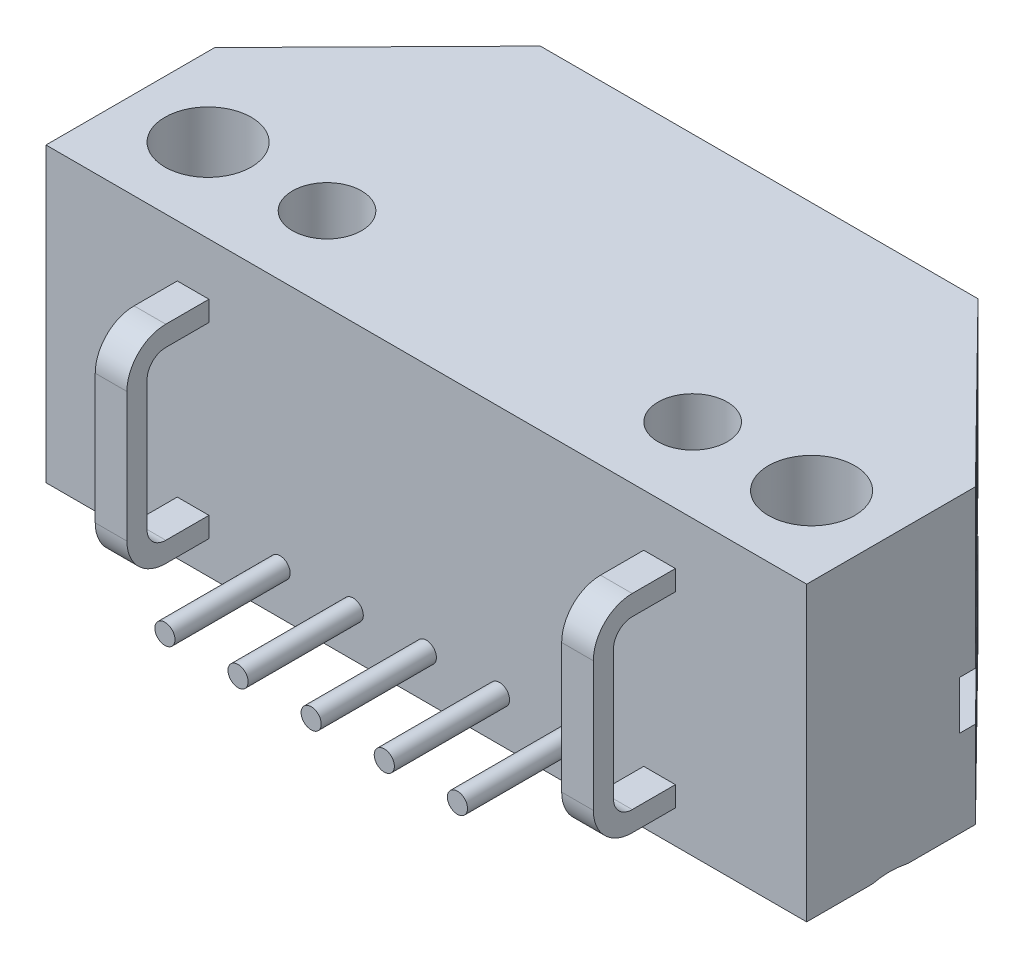
SolidWorks part; units mm, degrees
ref_plane "Ebene vorne" through (0, 0, 0) normal (0, 0, 1) x (1, 0, 0)
ref_plane "Ebene oben" through (0, 0, 0) normal (0, 1, 0) x (1, 0, 0)
ref_plane "Ebene rechts" through (0, 0, 0) normal (1, 0, 0) x (0, 0, -1)
sketch "Skizze1" plane through (0, 0, 0) normal (0, 1, 0) x (1, 0, 0)
  line L0 (0, 18.4765) -> (0, -25.5527) construction
  line L1 (-10.8738, -15.75) -> (10.2359, -15.75) construction
  line L2 (-12.2657, 0) -> (14.2955, 0) construction
  line L3 (-13.21, -18.65) -> (-13.21, -12.79)
  line L4 (-13.21, -12.79) -> (-7.6, -7.09)
  line L5 (-7.6, -7.09) -> (7.6, -7.09)
  line L6 (-13.21, -18.65) -> (13.21, -18.65)
  line L7 (13.21, -18.65) -> (13.21, -12.79)
  line L8 (13.21, -12.79) -> (7.6, -7.09)
  circle A0 centre (-10.48, -15.75) radius 1.385
  circle A1 centre (10.48, -15.75) radius 1.385
  point P17 (0, -18.65)
  point P19 (0, -7.09)
  dimension "D2" = 2.77
  dimension "D1" = 15.75
  dimension "D3" = 26.42
  dimension "D4" = 11.56
  dimension "D5" = 5.7
  dimension "D6" = 15.2
  dimension "D7" = 2.9
  dimension "D8" = 20.96
extrude "Aufsatz-Linear austragen1" add sketch "Skizze1" along normal blind 6.74 and the other way blind 3.42
sketch "Skizze2" plane through (0, 0, 0) normal (1, 0, 0) x (0, 0, -1)
  line L0 (-22.1031, 0) -> (8.1421, 0) construction
  line L1 (-13.35, 1.28) -> (2.6852, 1.28)
  line L2 (-13.35, 1.28) -> (-13.35, -0.4)
  line L3 (-13.35, -0.4) -> (2.6852, -0.4)
  line L4 (2.6852, 1.28) -> (2.6852, -0.4)
  line L5 (-7.09, -3.42) -> (-12.79, -3.42) construction
  line L6 (-7.09, 6.74) -> (-12.79, 6.74) construction
  line L7 (-18.65, -3.42) -> (-18.65, 6.74) construction
  dimension "D1" = 3.02
  dimension "D2" = 5.46
  dimension "D3" = 1.68
  dimension "D4" = 5.3
extrude "Schnitt-Linear austragen1" cut sketch "Skizze2" against normal through all and the other way through all
sketch "Skizze3" plane through (0, 6.74, 0) normal (0, 1, 0) x (1, 0, 0)
  line L0 (0, -26.155) -> (0, 11.9895) construction
  line L1 (21.4405, 0) -> (-13.3752, 0) construction
  line L2 (-13.21, -18.65) -> (13.21, -18.65) construction
  circle A0 centre (6.35, -15.75) radius 1.2
  circle A1 centre (-6.35, -15.75) radius 1.2
  dimension "D3" = 2.4
  dimension "D1" = 12.7
  dimension "D2" = 2.9
extrude "Schnitt-Linear austragen2" cut sketch "Skizze3" against normal blind 2.16
sketch "Skizze4" plane through (0, 0, 18.65) normal (0, 0, 1) x (1, 0, 0)
  line L0 (0, -9.3032) -> (0, 8.8775) construction
  line L1 (0, -1.9) -> (8.502, -1.9) construction
  line L2 (-13.21, -3.42) -> (13.21, -3.42) construction
  circle A0 centre (0, -1.9) radius 0.35
  circle A1 centre (2.54, -1.9) radius 0.35
  circle A2 centre (5.08, -1.9) radius 0.35
  circle A3 centre (-2.54, -1.9) radius 0.35
  circle A4 centre (-5.08, -1.9) radius 0.35
  dimension "D1" = 0.7
  dimension "D2" = 2.54
  dimension "D3" = 2.54
  dimension "D4" = 1.52
extrude "Aufsatz-Linear austragen2" add sketch "Skizze4" along normal blind 4
ref_plane "Ebene1" through (8.1, 0, 0) normal (1, 0, 0) x (0, 0, -1)
sketch "Skizze5" plane through (8.1, 0, 0) normal (1, 0, 0) x (0, 0, -1)
  line L0 (-18.65, -1.92) -> (-20.15, -1.92)
  line L1 (-21.15, -0.92) -> (-21.15, 3.58)
  line L2 (-20.15, 4.58) -> (-18.65, 4.58)
  line L3 (-18.65, -3.42) -> (-18.65, 6.74) construction
  line L4 (-18.65, -3.42) -> (-12.79, -3.42) construction
  arc A0 (-20.15, 4.58) -> (-21.15, 3.58) centre (-20.15, 3.58) ccw
  arc A1 (-21.15, -0.92) -> (-20.15, -1.92) centre (-20.15, -0.92) ccw
  point P10 (-21.15, 4.58)
  point P13 (-21.15, -1.92)
  dimension "D4" = 1
  dimension "D1" = 1.5
  dimension "D2" = 6.5
  dimension "D3" = 2.5
extrude "Linear-Austragen-Dünn1" add sketch "Skizze5" along normal blind 0.55 and the other way blind 0.55 thin thin type mid plane wall 0.7
mirror "Spiegeln1" about plane through (0, 0, 0) normal (1, 0, 0) of "Linear-Austragen-Dünn1"
ref_axis "Achse1" through (0, -3.928, 0) along (0, 1, 0)
hole_wizard "Formsenkung für M3 Senkschraube mit Schlitz/Kreuzschlitz1" positions "Skizze7" profile "Skizze6" countersink size "M3" standard "ANSI Metrisch"
sketch "Skizze7" plane through (0, -3.42, 0) normal (0, -1, 0) x (-1, 0, 0)
  point P0 (-10.48, -15.75)
  point P3 (10.48, -15.75)
sketch "Skizze6" plane through (10.48, -3.42, 15.75) normal (1, 0, 0) x (0, 0, -1)
  line L0 (0, 0) -> (0, 11.9013)
  line L1 (0, 11.9013) -> (1.5, 11)
  line L2 (1.5, 11) -> (1.5, 1.3)
  line L3 (1.5, 1.3) -> (2.8, 0)
  line L5 (2.8, 0) -> (0, 0)
  line L6 (-1.5, 1.3) -> (-2.8, 0) construction
  line L10 (0, 11.9013) -> (-1.5, 11) construction
  line L11 (0, -6.35) -> (0, 107.95) construction
  dimension "Bohrerdurchmesser" = 3
  dimension "Bohrungstiefe" = 11
  dimension "Senkdurchmesser (Oben)" = 5.6
  dimension "Senkwinkel (Oben)" = 90
  dimension "Spitzenwinkel" = 118
